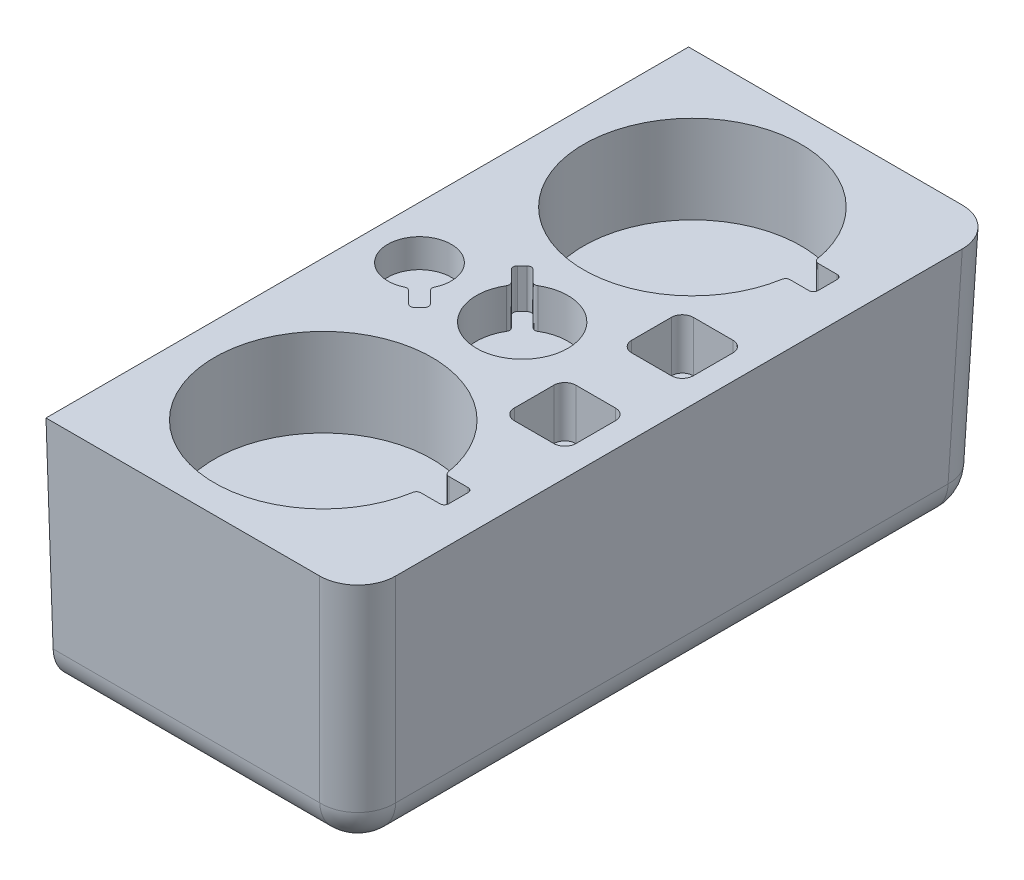
SolidWorks part; units mm, degrees
ref_plane "Front Plane" through (0, 0, 0) normal (0, 0, 1) x (1, 0, 0)
ref_plane "Top Plane" through (0, 0, 0) normal (0, 1, 0) x (1, 0, 0)
ref_plane "Right Plane" through (0, 0, 0) normal (1, 0, 0) x (0, 0, -1)
sketch "Sketch3" plane through (0, 0, 0) normal (0, 1, 0) x (1, 0, 0)
  line L1 (-68.945, -142.24) -> (68.945, -142.24)
  line L2 (-68.945, -142.24) -> (-68.945, 142.24)
  line L3 (-68.945, 142.24) -> (68.945, 142.24)
  line L4 (68.945, -142.24) -> (68.945, 142.24)
  line L5 (-68.945, -142.24) -> (68.945, 142.24) construction
  line L6 (-68.945, 142.24) -> (68.945, -142.24) construction
  point P0 (0, 0)
  dimension "D1" = 137.89
  dimension "D2" = 284.48
extrude "Boss-Extrude1" add sketch "Sketch3" along normal blind 109.22 draft 2 draft outward yes
sketch "Sketch1" plane through (0, 0, 0) normal (0, 1, 0) x (1, 0, 0)
  line L0 (43.981, 90.304) -> (56.381, 90.304)
  line L5 (56.381, 90.304) -> (56.381, 77.504)
  line L6 (56.381, 77.504) -> (43.981, 77.504)
  line L7 (43.981, -77.504) -> (56.381, -77.504)
  line L8 (56.381, -77.504) -> (56.381, -90.304)
  line L9 (56.381, -90.304) -> (43.981, -90.304)
  line L16 (38.583, 12.7) -> (56.583, 12.7)
  line L17 (33.583, 17.7) -> (33.583, 35.7)
  line L18 (38.583, 40.7) -> (56.583, 40.7)
  line L19 (61.583, 17.7) -> (61.583, 35.7)
  line L20 (33.583, 12.7) -> (61.583, 40.7) construction
  line L21 (33.583, 40.7) -> (61.583, 12.7) construction
  line L22 (38.583, -40.7) -> (56.583, -40.7)
  line L23 (33.583, -35.7) -> (33.583, -17.7)
  line L24 (38.583, -12.7) -> (56.583, -12.7)
  line L25 (61.583, -35.7) -> (61.583, -17.7)
  line L26 (33.583, -40.7) -> (61.583, -12.7) construction
  line L27 (33.583, -12.7) -> (61.583, -40.7) construction
  line L28 (-72.9829, 0) -> (75.943, 0) construction
  line L29 (72.759, 146.054) -> (-72.759, 146.054) construction
  line L31 (-72.759, 146.054) -> (-72.759, -146.054) construction
  line L34 (72.759, -146.054) -> (72.759, 146.054) construction
  line L35 (-72.759, -146.054) -> (72.759, -146.054) construction
  line L42 (-18.1092, 24.539) -> (-10.5432, 16.973)
  line L43 (-18.1092, 24.539) -> (-23.059, 19.5893)
  line L44 (-23.059, 19.5893) -> (-15.4929, 12.0232)
  line L45 (-20.5841, 22.0641) -> (1.48, 0) construction
  line L46 (-45.2054, 0) -> (-27.5137, -17.6916) construction
  line L47 (-37.7668, -12.3883) -> (-29.9886, -20.1665)
  line L48 (-29.9886, -20.1665) -> (-25.0389, -15.2167)
  line L49 (-25.0389, -15.2167) -> (-32.817, -7.4386)
  arc A0 (43.981, 90.304) -> (43.981, 77.504) centre (-5.053, 83.904) ccw
  arc A1 (43.981, -77.504) -> (43.981, -90.304) centre (-5.053, -83.904) ccw
  arc A4 (56.583, 40.7) -> (61.583, 35.7) centre (56.583, 35.7) cw
  arc A5 (56.583, 12.7) -> (61.583, 17.7) centre (56.583, 17.7) ccw
  arc A6 (38.583, 12.7) -> (33.583, 17.7) centre (38.583, 17.7) cw
  arc A7 (33.583, 35.7) -> (38.583, 40.7) centre (38.583, 35.7) cw
  arc A8 (38.583, -40.7) -> (33.583, -35.7) centre (38.583, -35.7) cw
  arc A9 (56.583, -40.7) -> (61.583, -35.7) centre (56.583, -35.7) ccw
  arc A10 (56.583, -12.7) -> (61.583, -17.7) centre (56.583, -17.7) cw
  arc A11 (33.583, -17.7) -> (38.583, -12.7) centre (38.583, -17.7) cw
  arc A12 (-32.817, -7.4386) -> (-37.7668, -12.3883) centre (-45.2054, 0) ccw
  arc A16 (-15.4929, 12.0232) -> (-10.5432, 16.973) centre (1.48, 0) ccw
  circle A17 centre (47.583, 26.7) radius 8.35
  circle A18 centre (47.583, -26.7) radius 8.35
  point P13 (47.583, 12.7)
  point P25 (47.583, 26.7)
  point P42 (47.583, -26.7)
  dimension "D3" = 98.9
  dimension "D4" = 98.9
  dimension "D8" = 20.8
  dimension "D11" = 11.303
  dimension "D15" = 5
  dimension "D18" = 5
  dimension "D5" = 12.7
  dimension "D19" = 18.256
  dimension "D20" = 12.7
  dimension "D21" = 28.9
  dimension "D22" = 135
  dimension "D23" = 7
  dimension "D25" = 12.7
  dimension "D12" = 13.1037
  dimension "D13" = 45
  dimension "D27" = 16.7
  dimension "D1" = 12.4
  dimension "D2" = 12.8
  dimension "D6" = 12.8
  dimension "D7" = 12.4
  dimension "D9" = 7
  dimension "D10" = 10.7
  dimension "D14" = 28
  dimension "D16" = 28
  dimension "D17" = 28
  dimension "D24" = 11
  dimension "D26" = 11.176
fillet "Fillet1" radius 17.272 5 edges at (0, 0, -142.24) (0, 0, 142.24) (68.945, 0, 0) (70.852, 54.61, -144.147) (70.852, 54.61, 144.147)
extrude "Cut-Extrude1" cut sketch "Sketch1" against normal blind 40 from surface contours A0 L6 L5 L0 | A1 L9 L8 L7 starting at face at (19.6913, 109.22, 0)
extrude "Cut-Extrude2" cut sketch "Sketch1<4>" against normal blind 13 from surface contours L49 A12 L47 L48 region at (-43.779, 0, 1.4263) starting at face at (25.56, 109.22, 83.904)
sketch "Sketch1<4>" plane through (0, 0, 0) normal (0, 1, 0) x (1, 0, 0) same geometry as "Sketch1"
extrude "Cut-Extrude3" cut sketch "Sketch1<5>" against normal blind 18 from surface contours L44 A16 L42 L43 region at (0.5384, 0, -0.9416) starting at face at (-36.4356, 109.22, 8.7697)
sketch "Sketch1<5>" plane through (0, 0, 0) normal (0, 1, 0) x (1, 0, 0) same geometry as "Sketch1"
extrude "Cut-Extrude5" cut sketch "Sketch1<6>" against normal blind 23 from surface contours A7 L17 A6 L16 A5 L19 A4 L18 | A11 L23 A8 L22 A9 L25 A10 L24 region at (35.3275, 0, -14.4445) region at (35.3275, 0, 38.9555) starting at face at (-9.4996, 109.22, -10.9796)
sketch "Sketch1<6>" plane through (0, 0, 0) normal (0, 1, 0) x (1, 0, 0) same geometry as "Sketch1"
extrude "Cut-Extrude7" cut sketch "Sketch1<7>" against normal blind 31 from surface contours A17 | A18 region at (47.583, 0, -26.7) region at (47.583, 0, 26.7) starting at face at (47.583, 109.22, 26.7)
sketch "Sketch1<7>" plane through (0, 0, 0) normal (0, 1, 0) x (1, 0, 0) same geometry as "Sketch1"
fillet "Fillet2" radius 2 16 edges at (43.981, 89.22, 90.304) (43.981, 89.22, 77.504) (56.381, 89.22, 77.504) (56.381, 89.22, 90.304) (-29.9886, 102.72, 20.1665) (-25.0389, 102.72, 15.2167) (-32.817, 102.72, 7.4386) (-37.7668, 102.72, 12.3883) (-15.4929, 100.22, -12.0232) (-23.059, 100.22, -19.5893) (-18.1092, 100.22, -24.539) (-10.5432, 100.22, -16.973) (43.981, 89.22, -77.504) (56.381, 89.22, -90.304) (56.381, 89.22, -77.504) (43.981, 89.22, -90.304)
sketch "Sketch4" plane through (0, 0, 0) normal (0, 0, 1) x (1, 0, 0)
  line L1 (-72.759, 109.22) -> (55.4976, 109.22) construction
  line L2 (-68.945, 109.22) -> (-68.945, 0)
  line L3 (-68.945, 0) -> (-84.2087, 109.22)
  line L4 (-84.2087, 109.22) -> (-68.945, 109.22)
  point P0 (-68.945, 0)
  point P5 (-84.2087, 109.22)
  point P9 (0, 0)
  dimension "D2" = 110.2814
extrude "Cut-Extrude8" cut sketch "Sketch4" against normal through all both and the other way through all contours L3 L4 L2
